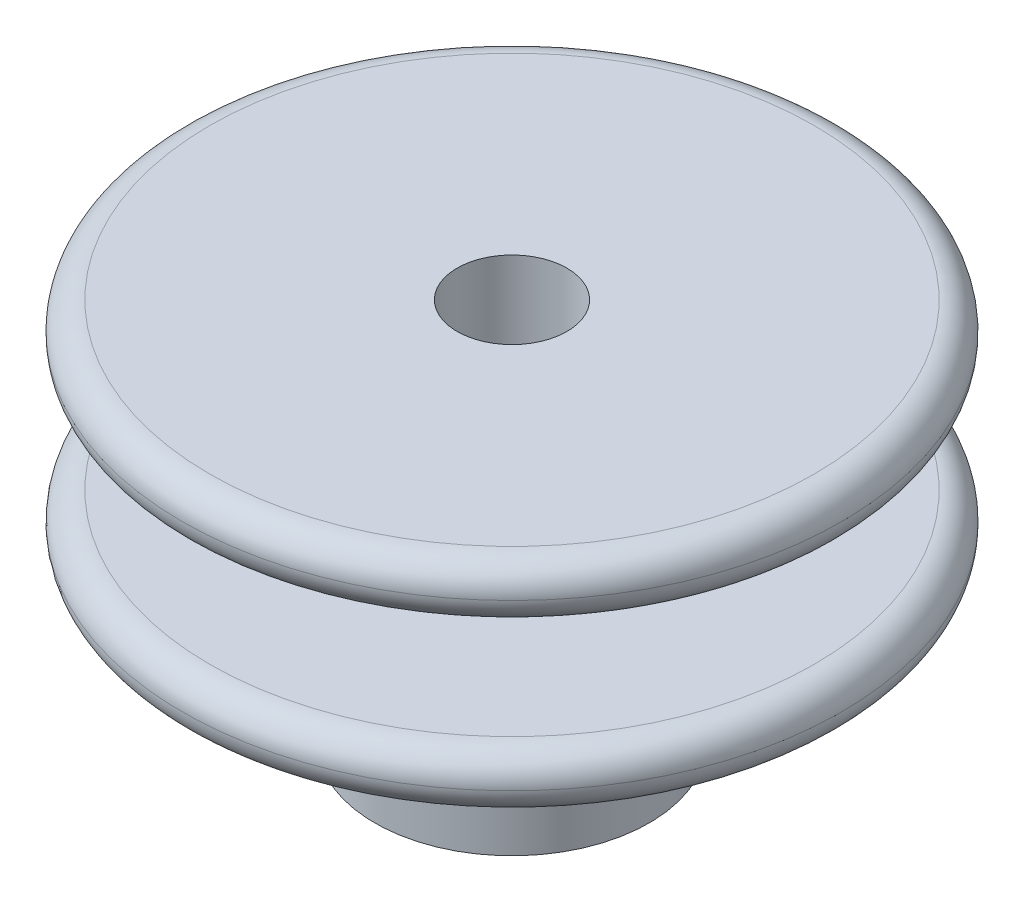
SolidWorks part; units mm, degrees
ref_plane "前视基准面" through (0, 0, 0) normal (0, 0, 1) x (1, 0, 0)
ref_plane "上视基准面" through (0, 0, 0) normal (0, 1, 0) x (1, 0, 0)
ref_plane "右视基准面" through (0, 0, 0) normal (1, 0, 0) x (0, 0, -1)
other "Configuration Table"
sketch "草图1" plane through (0, 0, 0) normal (0, 1, 0) x (1, 0, 0)
  circle A0 centre (0, 0) radius 5
  dimension "D1" = 10
extrude "凸台-拉伸1" add sketch "草图1" along normal blind 4
sketch "草图2" plane through (0, 4, 0) normal (0, 1, 0) x (1, 0, 0)
  circle A0 centre (0, 0) radius 12
  dimension "D1" = 24
extrude "凸台-拉伸2" add sketch "草图2" along normal blind 2
sketch "草图3" plane through (0, 0, 0) normal (0, -1, 0) x (1, 0, 0)
  circle A0 centre (0, 0) radius 12
  dimension "D1" = 24
extrude "凸台-拉伸3" add sketch "草图3" along normal blind 2
sketch "草图4" plane through (0, -2, 0) normal (0, -1, 0) x (-1, 0, 0)
  circle A0 centre (0, 0) radius 5
extrude "凸台-拉伸4" add sketch "草图4" along normal blind 6
sketch "草图5" plane through (0, -8, 0) normal (0, -1, 0) x (1, 0, 0)
  circle A0 centre (0, 0) radius 2
extrude "切除-拉伸1" cut sketch "草图5" against normal through all
fillet "圆角2" radius 1 4 edges at (0, 0, -12) (0, 4, 12) (0, 6, 12) (0, -2, -12)
